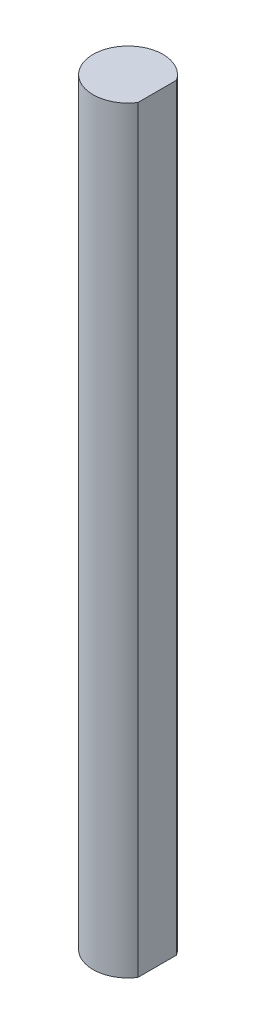
SolidWorks part; units mm, degrees
ref_plane "Front" through (0, 0, 0) normal (0, 0, 1) x (1, 0, 0)
ref_plane "Top" through (0, 0, 0) normal (0, 1, 0) x (1, 0, 0)
ref_plane "Right" through (0, 0, 0) normal (1, 0, 0) x (0, 0, -1)
sketch "Sketch1" plane through (0, 0, 0) normal (0, 1, 0) x (1, 0, 0)
  line L0 (-3, 0) -> (2.5, 0)
  line L1 (2.5, 0) -> (2.5, 1.6583)
  line L2 (2.5, 1.6583) -> (2.5, -1.6583)
  circle A0 centre (0, 0) radius 3
  dimension "D1" = 5.5
extrude "Boss-Extrude1" add sketch "Sketch1" along normal blind 65 contours L1 A0 L0 | L0 A0 L2 region at (-0.112, 0, -1.2999) region at (-0.112, 0, 1.2999)
